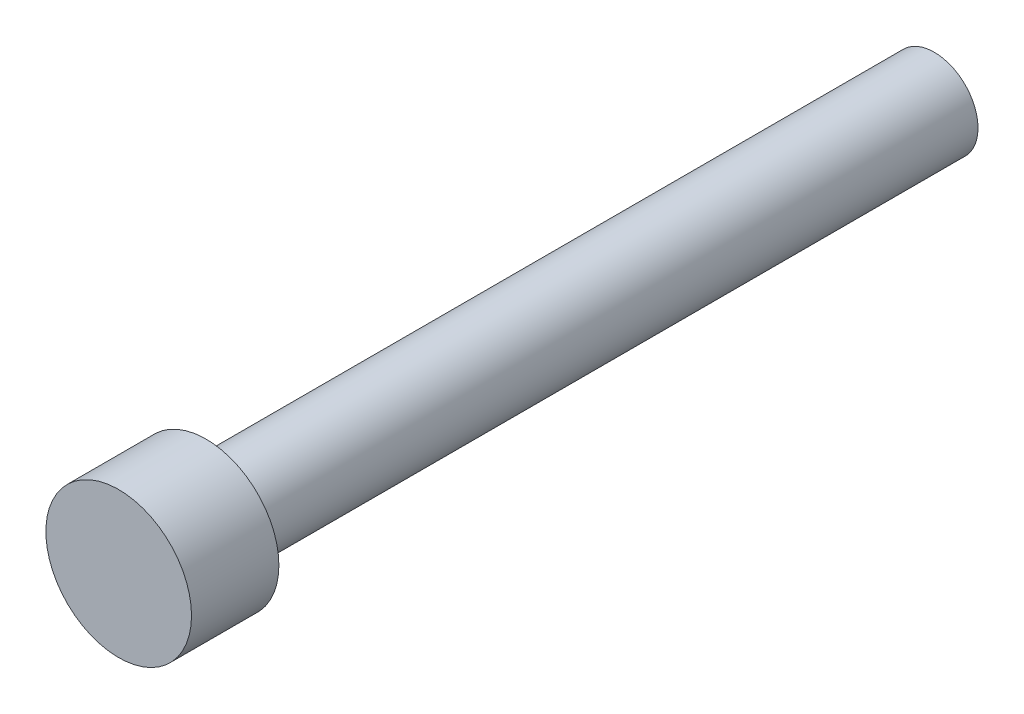
SolidWorks part; units mm, degrees
ref_plane "Alzado" through (0, 0, 0) normal (0, 0, 1) x (1, 0, 0)
ref_plane "Planta" through (0, 0, 0) normal (0, 1, 0) x (1, 0, 0)
ref_plane "Vista lateral" through (0, 0, 0) normal (1, 0, 0) x (0, 0, -1)
sketch "Croquis1" plane through (0, 0, 0) normal (0, 0, 1) x (1, 0, 0)
  circle A0 centre (0, 0) radius 1.5
  circle A1 centre (0, 0) radius 2.5
  dimension "D1" = 3
  dimension "D2" = 5
extrude "Saliente-Extruir1" add sketch "Croquis1" along normal blind 3 contours A0 | A1 A0 region at (0, 0, 0) region at (-2.4293, 0, 0)
extrude "Saliente-Extruir2" add sketch "Croquis1<3>" against normal blind 25 contours A0 region at (0, 0, 0)
sketch "Croquis1<3>" plane through (0, 0, 0) normal (0, 0, 1) x (1, 0, 0) same geometry as "Croquis1"
